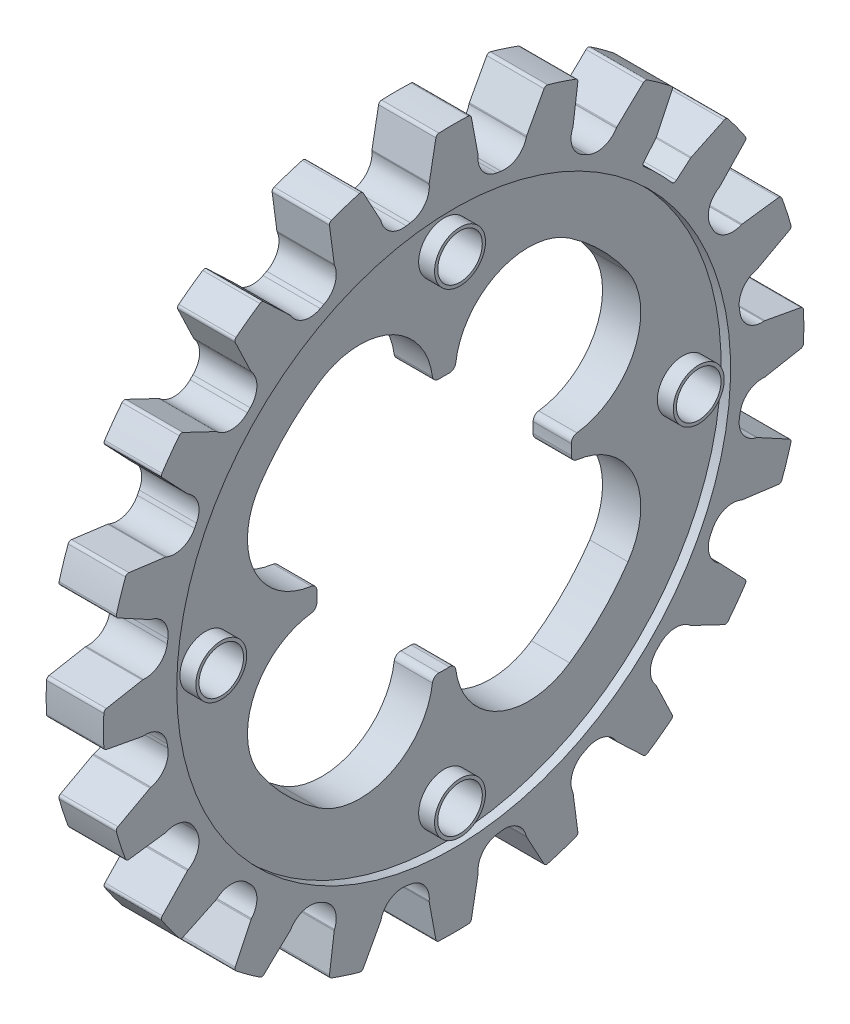
SolidWorks part; units mm, degrees
ref_plane "Спереди" through (0, 0, 0) normal (0, 0, 1) x (1, 0, 0)
ref_plane "Сверху" through (0, 0, 0) normal (0, 1, 0) x (1, 0, 0)
ref_plane "Справа" through (0, 0, 0) normal (1, 0, 0) x (0, 0, -1)
sketch "Эскиз2" plane through (0, 0, 0) normal (0, 0, 1) x (1, 0, 0)
  line L0 (-1000, 0) -> (49000, 0) construction
  line L1 (0, 40) -> (18, 40)
  line L2 (0, 40) -> (0, 110)
  line L3 (0, 110) -> (18, 110)
  line L4 (18, 40) -> (18, 110)
  dimension "D1" = 40
  dimension "D2" = 70
  dimension "D3" = 18
revolve "Повернуть1" add sketch "Эскиз2" angle 360 about L0
sketch "Эскиз7" plane through (0, 0, 0) normal (0, 0, 1) x (1, 0, 0)
  line L0 (18, 87) -> (15, 87)
  line L1 (18, -110) -> (18, 110) construction
  line L2 (15, 87) -> (15, 40)
  line L3 (15, 40) -> (18, 40)
  line L4 (18, -40) -> (18, 40) construction
  line L5 (18, 40) -> (18, 87)
  line L6 (9, -999.3149) -> (9, 49000.6851) construction
  line L7 (0, 40) -> (0, -40) construction
  line L8 (0, 87) -> (3, 87)
  line L9 (0, 40) -> (0, 87)
  line L10 (3, 40) -> (0, 40)
  line L11 (3, 87) -> (3, 40)
  line L12 (-1000, 0) -> (49000, 0) construction
  dimension "D1" = 6
  dimension "D2" = 40
  dimension "D3" = 87
revolve "Вырез-Повернуть3" cut sketch "Эскиз7" angle 360 about L12
ref_plane "Плоскость5" through (0, 0, 0) normal (0, 0.7071, 0.7071) x (1, 0, 0)
sketch "Эскиз8" plane through (0, 0, 0) normal (0, 0.7071, 0.7071) x (1, 0, 0)
  line L0 (-1000, 0) -> (49000, 0) construction
  line L1 (-5.5943, 69.9577) -> (27.0624, 69.9577)
  line L2 (-5.5943, 69.9577) -> (-5.5943, 24.9577)
  line L3 (-5.5943, 24.9577) -> (27.0624, 24.9577)
  line L4 (27.0624, 69.9577) -> (27.0624, 24.9577)
  dimension "D1" = 45
  dimension "D2" = 32.6567
  dimension "D3" = 24.9577
  dimension "D4" = 27.0624
revolve "Вырез-Повернуть4" cut sketch "Эскиз8" angle 80 mid plane about L0
pattern_circular "Круговой массив1" count 4 over 360 about axis through (-1000, 0, 0) along (-1, 0, 0) of "Вырез-Повернуть4" reverse direction yes
sketch "Эскиз12" plane through (0, 0, 0) normal (0, 0, 1) x (1, 0, 0)
  line L0 (15, 82) -> (3, 82)
  line L1 (15, -87) -> (15, 87) construction
  line L2 (3, 87) -> (3, -87) construction
  line L3 (3, 82) -> (3, 75)
  line L5 (3, 75) -> (15, 75)
  line L7 (15, 75) -> (15, 82)
  dimension "D1" = 82
  dimension "D2" = 7
revolve "Вырез-Повернуть5" cut sketch "Эскиз12" angle 360 about L5
ref_axis "Ось2" through (23.4681, 75, 0) along (-1, 0, 0)
sketch "Эскиз13" plane through (0, 0, 0) normal (0, 0, 1) x (1, 0, 0)
  line L0 (15, 83) -> (20, 83)
  line L1 (20, 83) -> (20, 82)
  line L2 (20, 82) -> (15, 82)
  line L3 (15, 82) -> (15, 83)
  line L4 (9, -968.1016) -> (9, 49031.8984) construction
  line L5 (15, 6.0972) -> (15, 69.6914) construction
  line L6 (3, 87) -> (3, -87) construction
  line L7 (3, 82) -> (3, 83)
  line L8 (3, 83) -> (-2, 83)
  line L9 (-2, 83) -> (-2, 82)
  line L10 (-2, 82) -> (3, 82)
  dimension "D1" = 5
  dimension "D2" = 1
  dimension "D3" = 82
  dimension "D4" = 6
revolve "Повернуть3" add sketch "Эскиз13" angle 360 about axis through (23.4681, 75, 0) along (-1, 0, 0)
ref_axis "Ось3" through (142.0173, 0, 0) along (-1, 0, 0)
pattern_circular "Круговой массив2" count 4 over 360 about axis through (142.0173, 0, 0) along (-1, 0, 0) of "Повернуть3", "Вырез-Повернуть5"
sketch "Эскиз15" plane through (0, 0, 0) normal (0, 0.7071, 0.7071) x (1, 0, 0)
  line L0 (0, 110) -> (0, -110) construction
  line L1 (0, 118.7964) -> (42.7614, 118.7964)
  line L2 (0, 118.7964) -> (0, 91)
  line L3 (0, 91) -> (42.7614, 91)
  line L4 (42.7614, 118.7964) -> (42.7614, 91)
  point P4 (30.5676, 93.54)
  point P5 (30.8728, 91.1715)
  dimension "D1" = 42.7614
  dimension "D2" = 27.7964
  dimension "D3" = 91
revolve "Вырез-Повернуть6" cut sketch "Эскиз15" angle 9 mid plane about axis through (142.0173, 0, 0) along (-1, 0, 0)
pattern_circular "Круговой массив3" count 20 over 360 about axis through (142.0173, 0, 0) along (-1, 0, 0) of "Вырез-Повернуть6"
fillet "Скругление1" radius 7 38 edges at (9, 84.073, -34.8242) (9, 77.5903, -47.5474) (9, 88.4857, 21.2435) (9, 90.7195, 7.1398) (9, 77.5903, 47.5474) (9, 84.073, 34.8242) (9, 59.0998, 69.1969) (9, 69.1969, 59.0998) (9, 34.8242, 84.073) (9, 47.5474, 77.5903) (9, 7.1398, 90.7195) (9, 21.2435, 88.4857) (9, -21.2435, 88.4857) (9, -7.1398, 90.7195) (9, -47.5474, 77.5903) (9, -34.8242, 84.073) (9, -69.1969, 59.0998) (9, -59.0998, 69.1969) (9, -84.073, 34.8242) (9, -77.5903, 47.5474) (9, -90.7195, 7.1398) (9, -88.4857, 21.2435) (9, -88.4857, -21.2435) (9, -90.7195, -7.1398) (9, -77.5903, -47.5474) (9, -84.073, -34.8242) (9, -59.0998, -69.1969) (9, -69.1969, -59.0998) (9, -34.8242, -84.073) (9, -47.5474, -77.5903) (9, -7.1398, -90.7195) (9, -21.2435, -88.4857) (9, 21.2435, -88.4857) (9, 7.1398, -90.7195) (9, 47.5474, -77.5903) (9, 34.8242, -84.073) (9, 88.4857, -21.2435) (9, 90.7195, -7.1398)
chamfer "Фаска1" distance 12 angle 15 20 edges at (9, 109.6609, -8.6305) (9, 106.9607, 25.679) (9, 93.7904, 57.4748) (9, 71.4393, 83.6447) (9, 42.0952, 101.6267) (9, 8.6305, 109.6609) (9, -25.679, 106.9607) (9, -57.4748, 93.7904) (9, -83.6447, 71.4393) (9, -101.6267, 42.0952) (9, -109.6609, 8.6305) (9, -106.9607, -25.679) (9, -93.7904, -57.4748) (9, -71.4393, -83.6447) (9, -42.0952, -101.6267) (9, -8.6305, -109.6609) (9, 25.679, -106.9607) (9, 57.4748, -93.7904) (9, 83.6447, -71.4393) (9, 101.6267, -42.0952) first distance on face at (9, 103.5546, -8.1499) first distance on face at (9, 101.0048, 24.2491) first distance on face at (9, 88.5679, 54.2745) first distance on face at (9, 67.4613, 78.987) first distance on face at (9, 39.7512, 95.9678) first distance on face at (9, 8.1499, 103.5546) first distance on face at (9, -24.2491, 101.0048) first distance on face at (9, -54.2745, 88.5679) first distance on face at (9, -78.987, 67.4613) first distance on face at (9, -95.9678, 39.7512) first distance on face at (9, -103.5546, 8.1499) first distance on face at (9, -101.0048, -24.2491) first distance on face at (9, -88.5679, -54.2745) first distance on face at (9, -67.4613, -78.987) first distance on face at (9, -39.7512, -95.9678) first distance on face at (9, -8.1499, -103.5546) first distance on face at (9, 24.2491, -101.0048) first distance on face at (9, 54.2745, -88.5679) first distance on face at (9, 76.4208, -65.2695) first distance on face at (9, 95.9678, -39.7512)
chamfer "Фаска2" distance 12 angle 15 20 edges at (9, 42.0952, -101.6267) (9, 8.6305, -109.6609) (9, -25.679, -106.9607) (9, -57.4748, -93.7904) (9, -83.6447, -71.4393) (9, -101.6267, -42.0952) (9, -109.6609, -8.6305) (9, -106.9607, 25.679) (9, -93.7904, 57.4748) (9, -71.4393, 83.6447) (9, -42.0952, 101.6267) (9, -8.6305, 109.6609) (9, 25.679, 106.9607) (9, 57.4748, 93.7904) (9, 83.6447, 71.4393) (9, 101.6267, 42.0952) (9, 71.4393, -83.6447) (9, 93.7904, -57.4748) (9, 106.9607, -25.679) (9, 109.6609, 8.6305) first distance on face at (9, 39.7512, -95.9678) first distance on face at (9, 8.1499, -103.5546) first distance on face at (9, -24.2491, -101.0048) first distance on face at (9, -54.2745, -88.5679) first distance on face at (9, -78.987, -67.4613) first distance on face at (9, -95.9678, -39.7512) first distance on face at (9, -103.5546, -8.1499) first distance on face at (9, -101.0048, 24.2491) first distance on face at (9, -88.5679, 54.2745) first distance on face at (9, -67.4613, 78.987) first distance on face at (9, -39.7512, 95.9678) first distance on face at (9, -8.1499, 103.5546) first distance on face at (9, 24.2491, 101.0048) first distance on face at (9, 54.2745, 88.5679) first distance on face at (9, 78.987, 67.4613) first distance on face at (9, 95.9678, 39.7512) first distance on face at (9, 65.2695, -76.4208) first distance on face at (9, 88.5679, -54.2745) first distance on face at (9, 101.0048, -24.2491) first distance on face at (9, 103.5546, 8.1499)
fillet "Скругление2" radius 23 8 edges at (9, -6.0972, -69.6914) (9, 6.0972, 69.6914) (9, -6.0972, 69.6914) (9, -69.6914, 6.0972) (9, -69.6914, -6.0972) (9, 69.6914, -6.0972) (9, 6.0972, -69.6914) (9, 69.6914, 6.0972)
fillet "Скругление4" radius 1 82 edges at (9, 28.7825, -106.1676) (9, 22.8776, -95.2923) (9, 7.689, -97.6979) (9, 5.4338, -109.8657) (9, -5.4338, -109.8657) (9, -7.689, -97.6979) (9, -22.8776, -95.2923) (9, -28.7825, -106.1676) (9, -39.1182, -102.8094) (9, -37.503, -90.5402) (9, -51.2049, -83.5587) (9, -60.1814, -92.0771) (9, -68.9735, -85.6893) (9, -63.6459, -74.5198) (9, -74.5198, -63.6459) (9, -85.6893, -68.9735) (9, -92.0771, -60.1814) (9, -83.5587, -51.2049) (9, -90.5402, -37.503) (9, -102.8094, -39.1182) (9, -106.1676, -28.7825) (9, -95.2923, -22.8776) (9, -97.6979, -7.689) (9, -109.8657, -5.4338) (9, -109.8657, 5.4338) (9, -97.6979, 7.689) (9, -95.2923, 22.8776) (9, -106.1676, 28.7825) (9, -102.8094, 39.1182) (9, -90.5402, 37.503) (9, -83.5587, 51.2049) (9, -92.0771, 60.1814) (9, -85.6893, 68.9735) (9, -74.5198, 63.6459) (9, -63.6459, 74.5198) (9, -68.9735, 85.6893) (9, -60.1814, 92.0771) (9, -51.2049, 83.5587) (9, -37.503, 90.5402) (9, -39.1182, 102.8094) (9, -28.7825, 106.1676) (9, -22.8776, 95.2923) (9, -7.689, 97.6979) (9, -5.4338, 109.8657) (9, 5.4338, 109.8657) (9, 7.689, 97.6979) (9, 22.8776, 95.2923) (9, 28.7825, 106.1676) (9, 39.1182, 102.8094) (9, 37.503, 90.5402) (9, 51.2049, 83.5587) (9, 60.1814, 92.0771) (9, 68.9735, 85.6893) (9, 63.6459, 74.5198) (9, 74.5198, 63.6459) (9, 85.6893, 68.9735) (9, 92.0771, 60.1814) (9, 83.5587, 51.2049) (9, 90.5402, 37.503) (9, 102.8094, 39.1182) (9, 95.2923, 22.8776) (9, 97.6979, 7.689) (9, 109.8657, 5.4338) (9, 97.6979, -7.689) (9, 95.2923, -22.8776) (9, 106.1676, -28.7825) (9, 102.8094, -39.1182) (9, 90.5402, -37.503) (9, 83.5587, -51.2049) (9, 92.0771, -60.1814) (9, 85.6893, -68.9735) (9, 74.5198, -63.6459) (9, 69.1969, -59.0998) (9, 59.0998, -69.1969) (9, 63.6459, -74.5198) (9, 68.9735, -85.6893) (9, 60.1814, -92.0771) (9, 51.2049, -83.5587) (9, 37.503, -90.5402) (9, 39.1182, -102.8094) (9, 106.1676, 28.7825) (9, 109.8657, -5.4338)
fillet "Скругление5" radius 2 8 edges at (9, -39.8478, -3.4862) (9, -39.8478, 3.4862) (9, 39.8478, 3.4862) (9, 3.4862, -39.8478) (9, -3.4862, -39.8478) (9, 39.8478, -3.4862) (9, -3.4862, 39.8478) (9, 3.4862, 39.8478)
